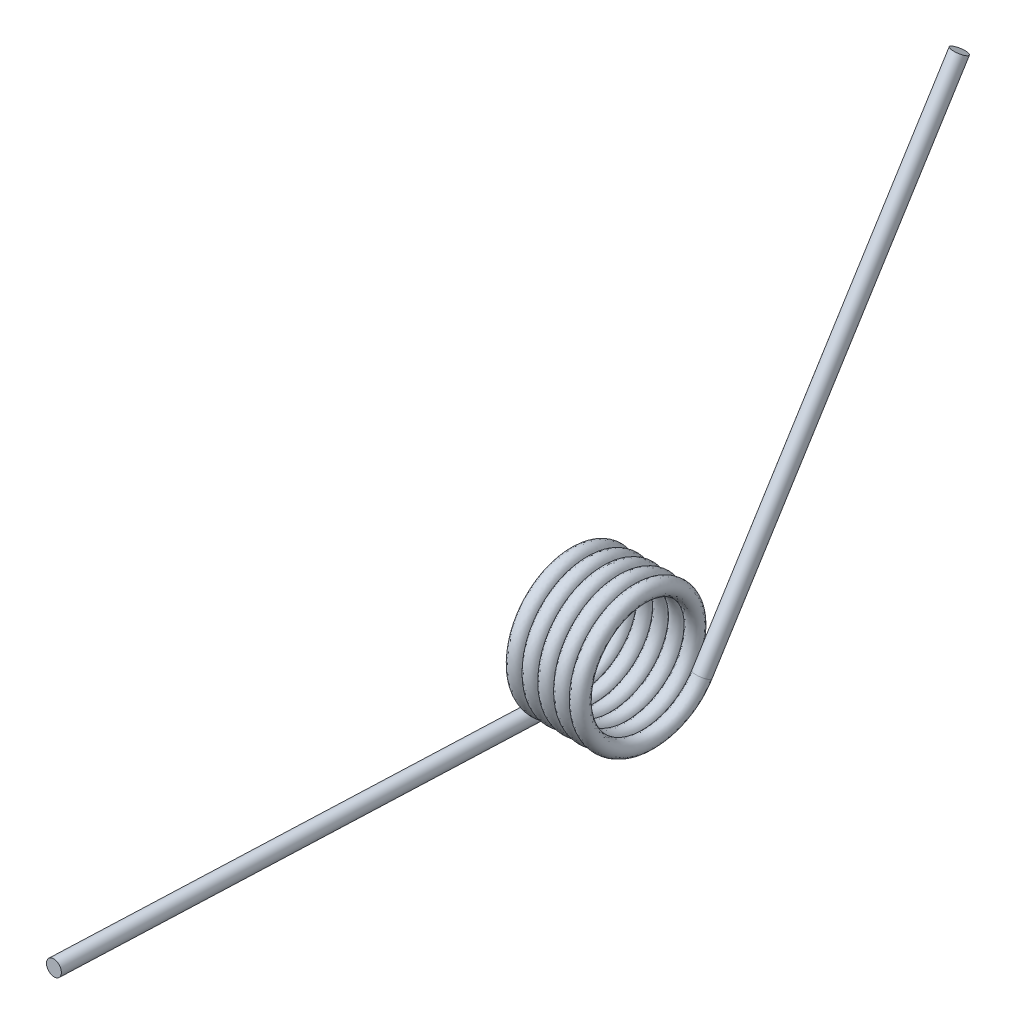
SolidWorks part; units mm, degrees
ref_plane "Front" through (0, 0, 0) normal (0, 0, 1) x (1, 0, 0)
ref_plane "Top" through (0, 0, 0) normal (0, 1, 0) x (1, 0, 0)
ref_plane "Right" through (0, 0, 0) normal (1, 0, 0) x (0, 0, -1)
sketch "Sketch1" plane through (0, 0, 0) normal (1, 0, 0) x (0, 0, -1)
  line L0 (0, 0) -> (0, -5.5118) construction
  line L1 (0, -5.5118) -> (0, -6.3119) construction
  line L2 (0, -6.3119) -> (0, -7.112) construction
  line L3 (0, 7.112) -> (0, -7.112) construction
  circle A0 centre (0, 0) radius 5.5118 construction
  circle A1 centre (0, 0) radius 7.112 construction
  circle A2 centre (0, 0) radius 6.3119
  circle A3 centre (0, -6.3119) radius 0.8001 construction
  circle A4 centre (0, 0) radius 4.3561 construction
  dimension "Wire Dia" = 1.6002
  dimension "Spring OD" = 14.224
  dimension "Max Rod OD" = 8.7122
curve "Helix/Spiral1" pitch 1.6256 height 8.4044 radius 6.3119 centre (0, 0, 0) axis (1, 0, 0) start towards (0, 0, -1)
ref_plane "Plane1" through (0, -6.3119, 0) normal (0.041, 0, -0.9992) x (0.9952, 0.0889, 0.0408)
sketch "Sketch2" plane through (0, -6.3119, 0) normal (0.041, 0, -0.9992) x (0.9952, 0.0889, 0.0408)
  circle A0 centre (0, 0) radius 0.8001
  dimension "D1" = 1.6002
sweep "Sweep1" add profiles "Sketch2" path "Helix/Spiral1"
sketch "Sketch3" plane through (0, 0, 0) normal (-0.041, 0, 0.9992) x (-0.9952, -0.0889, -0.0408)
  circle A1 centre (0.5611, 6.2869) radius 0.8001
  circle A2 centre (0.5611, 6.2869) radius 0.8001
  dimension "D1" = 0
extrude "Extrude1" add sketch "Sketch3" along normal blind 50.8
sketch "Sketch4" plane through (0.0141, 0.3014, -0.1657) normal (0.041, 0.8756, -0.4813) x (0.9928, -0.09, -0.0792)
  circle A1 centre (9.0552, 5.3252) radius 0.8001
  circle A2 centre (9.0552, 5.3252) radius 0.8001
  dimension "D1" = 0
extrude "Extrude2" add sketch "Sketch4" along normal blind 50.8
sketch "Sketch5" plane through (0, 0, 0) normal (1, 0, 0) x (0, 0, -1)
  line L0 (-50.7574, -5.5118) -> (-50.7574, -7.112) construction
  circle A0 centre (0, 0) radius 4.3561 construction
  circle A1 centre (0, 0) radius 4.3561
equation "\"D4@Helix/Spiral1\"=\"Wire Dia@Sketch1\"+.001"
equation "\"D1@Sketch2\"=\"Wire Dia@Sketch1\""
equation "\"D1@Extrude2\"=\"Leg Length@Extrude1\""
